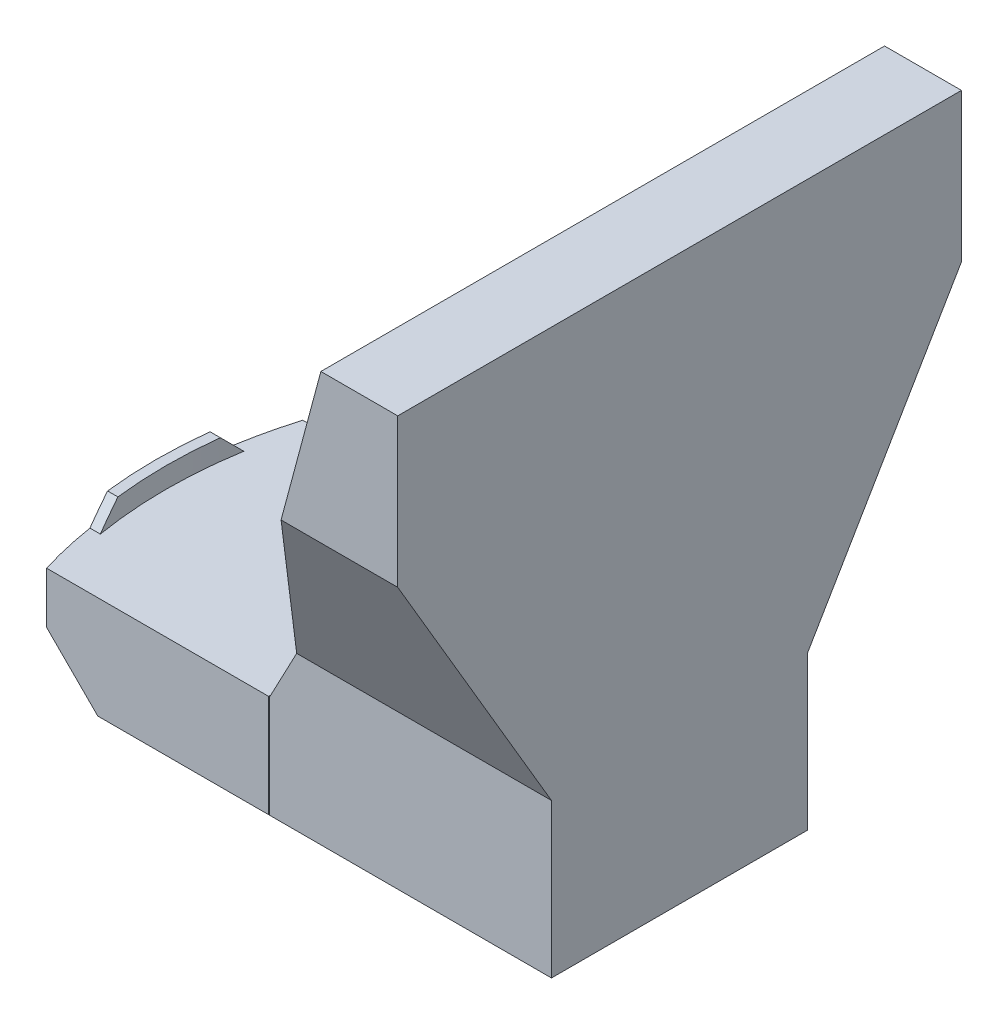
SolidWorks part; units mm, degrees
ref_plane "Płaszczyzna przednia" through (0, 0, 0) normal (0, 0, 1) x (1, 0, 0)
ref_plane "Płaszczyzna górna" through (0, 0, 0) normal (0, 1, 0) x (1, 0, 0)
ref_plane "Płaszczyzna prawa" through (0, 0, 0) normal (1, 0, 0) x (0, 0, -1)
sketch "Szkic1" plane through (0, 0, 0) normal (0, 1, 0) x (1, 0, 0)
  line L1 (22.8486, -15) -> (22.8486, 25)
  line L2 (22.8486, 25) -> (-20.4821, 25)
  line L3 (22.8486, -25) -> (22.8486, -15)
  line L5 (-20.4821, -25) -> (22.8486, -25)
  arc A0 (-20.4821, 25) -> (-22.8486, -15) centre (62.8486, 0) ccw
  arc A1 (-22.8486, -15) -> (-20.4821, -25) centre (62.8486, 0) ccw
extrude "Dodanie-wyciągnięcie1" add sketch "Szkic1" along normal blind 20
sketch "Szkic2" plane through (0, 0, 25) normal (0, 0, 1) x (1, 0, 0)
  line L1 (-20.4821, 0) -> (22.8486, 0) construction
  line L2 (-10.4821, 0) -> (-25.0364, 14.5543)
  line L3 (-25.0364, 14.5543) -> (-25.0364, -2.7354)
  line L4 (-25.0364, -2.7354) -> (-10.4821, -2.7354)
  line L5 (-10.4821, -2.7354) -> (-10.4821, 0)
extrude "Wytnij-wyciągnięcie1" cut sketch "Szkic2" against normal through all
sketch "Szkic3" plane through (0, 20, 0) normal (0, 1, 0) x (1, 0, 0)
  line L5 (-23.0176, -14) -> (-20.9906, -14)
  line L6 (-23.0176, 14) -> (-20.9906, 14)
  arc A0 (-20.4821, 25) -> (-20.4821, -25) centre (62.8486, 0) ccw construction
  arc A1 (-23.0176, 14) -> (-23.0176, -14) centre (62.8486, 0) ccw
  arc A2 (-20.9906, 14) -> (-20.9906, -14) centre (62.8486, 0) ccw
  arc A3 (-18.5664, 24.4253) -> (-18.5664, -24.4253) centre (62.8486, 0) ccw construction
  arc A4 (-20.4821, 25) -> (-20.4821, -25) centre (62.8486, 0) ccw construction
  dimension "D1" = 2
extrude "Dodanie-wyciągnięcie2" add sketch "Szkic3" along normal blind 4
chamfer "Sfazowanie1" distance 4 angle 45 2 edges at (-22.0041, 24, -14) (-22.0041, 24, 14)
sketch "Szkic4" plane through (0, 0, 25) normal (0, 0, 1) x (1, 0, 0)
  line L0 (63.0457, 110) -> (55.2811, 81.0222)
  line L1 (55.2811, 81.0222) -> (23.0457, 20)
  line L2 (23.0457, 20) -> (23.0457, 0)
  line L3 (23.0457, 0) -> (63.0457, 0)
  line L4 (78.0457, 110) -> (63.0457, 110)
  line L5 (78.0457, 110) -> (78.0457, 0)
  line L6 (78.0457, 0) -> (63.0457, 0)
extrude "Dodanie-wyciągnięcie3" add sketch "Szkic4" along normal up to surface (30 mm away) and the other way up to surface (80 mm away) separate body
sketch "Szkic5" plane through (78.0457, 0, 0) normal (1, 0, 0) x (0, 0, -1)
  line L0 (-55, 0) -> (-25, 0)
  line L1 (-55, 0) -> (55, 0) construction
  line L2 (-25, 0) -> (-25, 30)
  line L5 (-55, 81.0222) -> (-55, 0)
  line L6 (-55, 81.0222) -> (-25, 30)
  dimension "D1" = 30
  dimension "D2" = 30
extrude "Wytnij-wyciągnięcie2" cut sketch "Szkic5" against normal through all
ref_plane "Płaszczyzna1" through (0, 0, 0) normal (0, 0, 1) x (1, 0, 0)
ref_plane "Płaszczyzna2" through (0, 0, 0) normal (0, 0, 1) x (1, 0, 0)
mirror "Lustro1" about plane through (0, 0, 0) normal (0, 0, 1) of "Wytnij-wyciągnięcie2"
